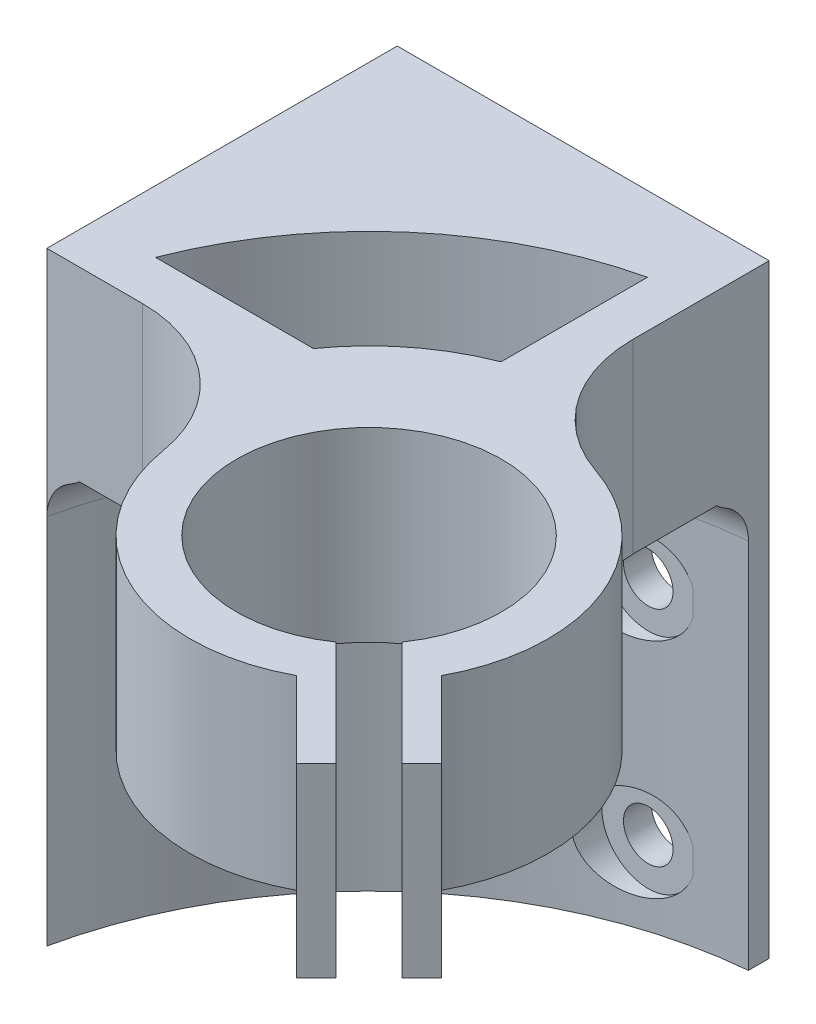
SolidWorks part; units mm, degrees
ref_plane "Front" through (0, 0, 0) normal (0, 0, 1) x (1, 0, 0)
ref_plane "Top" through (0, 0, 0) normal (0, 1, 0) x (1, 0, 0)
ref_plane "Right" through (0, 0, 0) normal (1, 0, 0) x (0, 0, -1)
sketch "Sketch1" plane through (0, 0, 0) normal (0, 1, 0) x (1, 0, 0)
  line L1 (-20, -5) -> (20, -5)
  line L2 (-20, -5) -> (-20, 5)
  line L3 (-20, 5) -> (20, 5)
  line L4 (20, -5) -> (20, 5)
  line L5 (-20, -5) -> (20, 5) construction
  line L6 (-20, 5) -> (20, -5) construction
  point P0 (0, 0)
  dimension "D1" = 40
  dimension "D2" = 10
extrude "Boss-Extrude1" add sketch "Sketch1" along normal blind 65
sketch "Sketch2" plane through (0, 65, 0) normal (0, 1, 0) x (1, 0, 0)
  arc A1 (-20.9979, -42.1234) -> (33.9588, 1.8676) centre (24.0871, -42.1234) ccw construction
sketch "Sketch3" plane through (0, 0, 0) normal (0, -1, 0) x (1, 0, 0)
  line L4 (20, -5) -> (20, 5)
  line L5 (20, 5) -> (-20, 5)
  line L6 (-20, 5) -> (-20, -5)
  line L7 (-20, -5) -> (20, -5)
  line L8 (20, -2.776) -> (20, 5)
  line L9 (20, 5) -> (-1.4963, 5)
  arc A0 (33.9588, -1.8676) -> (-20.9979, 42.1234) centre (24.0871, 42.1234) ccw construction
  arc A2 (-1.4963, 5) -> (20, -2.776) centre (24.0871, 42.1234) ccw
  dimension "D1" = 0
extrude "Cut-Extrude2" cut sketch "Sketch3" against normal up to next
sketch "Sketch4" plane through (0, 0, 0) normal (0, -1, 0) x (-1, 0, 0)
  line L0 (20, -5) -> (20, -32.6903)
  line L1 (20, -5) -> (1.4963, -5)
  arc A0 (20, -32.6903) -> (1.4963, -5) centre (-24.0871, -42.1234) ccw
extrude "Boss-Extrude2" add sketch "Sketch4" against normal up to surface (65 mm away) up to face at (-0.3995, 65, -0.8322)
sketch "Sketch5" plane through (0, 65, 0) normal (0, 1, 0) x (1, 0, 0)
  line L0 (-20, -32.6903) -> (7.3068, -32.6903)
  line L1 (20, 2.776) -> (20, -23.3123)
  line L2 (24.0871, -42.1234) -> (45.3003, -63.3366) construction
  line L3 (24.0871, -42.1234) -> (24.0871, -61.3734) construction
  line L4 (25.8549, -40.3556) -> (47.0681, -61.5688) construction
  line L5 (35.7749, -50.2756) -> (47.0681, -61.5688)
  line L6 (32.2394, -53.8111) -> (43.5326, -65.1044)
  line L7 (41.0206, -51.2787) -> (49.1894, -59.4475)
  line L8 (33.2424, -59.0569) -> (41.4112, -67.2257)
  line L9 (49.1894, -59.4475) -> (47.0681, -61.5688)
  line L10 (43.5326, -65.1044) -> (41.4112, -67.2257)
  line L11 (30.118, -55.9325) -> (41.4112, -67.2257) construction
  line L12 (37.8962, -48.1543) -> (49.1894, -59.4475) construction
  arc A0 (35.7749, -50.2756) -> (32.2394, -53.8111) centre (24.0871, -42.1234) ccw
  arc A1 (7.3068, -32.6903) -> (33.2424, -59.0569) centre (24.0871, -42.1234) ccw
  arc A2 (20, 2.776) -> (-20, -32.6903) centre (24.0871, -42.1234) ccw construction
  arc A3 (20, 2.776) -> (-20, -32.6903) centre (24.0871, -42.1234) ccw
  circle A4 centre (24.0871, -42.1234) radius 19.25 construction
  arc A5 (41.0206, -51.2787) -> (20, -23.3123) centre (24.0871, -42.1234) ccw
  circle A6 centre (24.0871, -42.1234) radius 14.25 construction
  dimension "D1" = 28.5
  dimension "D3" = 45
  dimension "D4" = 30
  dimension "D2" = 5
  dimension "D5" = 3
  dimension "D6" = 2.5
  dimension "D7" = 3
extrude "Boss-Extrude3" add sketch "Sketch5" against normal blind 20
fillet "Fillet1" radius 15 2 edges at (7.3068, 55, 32.6903) (20, 55, 23.3123)
fillet "Fillet2" radius 5 1 edges at (-5.8237, 45, 8.3891)
sketch "Sketch6" plane through (0, 45, 0) normal (0, -1, 0) x (1, 0, 0)
  line L0 (-13.3093, 27.6903) -> (3.6742, 27.6903)
  line L1 (15, 3.082) -> (15, 18.8334)
  line L2 (-14.8721, 32.6903) -> (-9.7074, 32.6903) construction
  line L3 (20, 9.6584) -> (20, 2.2473) construction
  arc A0 (3.6742, 27.6903) -> (15, 18.8334) centre (24.0871, 42.1234) ccw
  arc A1 (-14.8721, 32.6903) -> (20, 2.2473) centre (24.0871, 42.1234) ccw construction
  arc A2 (-13.3093, 27.6903) -> (15, 3.082) centre (24.0871, 42.1234) ccw
  dimension "D1" = 50
  dimension "D2" = 5
  dimension "D3" = 5
extrude "Cut-Extrude3" cut sketch "Sketch6" against normal up to next
fillet "Fillet3" radius 5 4 edges at (15, 45, 10.9577) (8.6867, 45, 22.4301) (-4.8176, 45, 27.6903) (-2.2107, 45, 11.8706)
sketch "Sketch7" plane through (-12.9072, 0, 12.9072) normal (-0.7071, 0, 0.7071) x (0.7071, 0, 0.7071)
  line L0 (71.0417, 45) -> (71.0417, 65) construction
  line L1 (65.2655, 45) -> (76.8179, 45) construction
  line L2 (65.2655, 65) -> (76.8179, 65) construction
  circle A0 centre (71.0417, 50) radius 2.665
  circle A1 centre (71.0417, 60) radius 2.665
  dimension "D1" = 5.33
  dimension "D2" = 5
  dimension "D3" = 5
extrude "Cut-Extrude4" cut sketch "Sketch7" against normal up to surface (11 mm away) up to face at (45.105, 55, 55.3631)
sketch "Sketch8" plane through (0, 0, -5) normal (0, 0, -1) x (-1, 0, 0)
  line L0 (-20, 40) -> (20, 40) construction
  line L1 (-20, 40) -> (20, 40) construction
  line L2 (-10, 40) -> (-10, 32) construction
  line L3 (0, 40) -> (0, 0) construction
  line L4 (-20, 0) -> (20, 0) construction
  line L5 (0, 20) -> (-20, 20) construction
  line L6 (-20, 65) -> (-20, 0) construction
  circle A0 centre (-10, 32) radius 2.665
  circle A1 centre (-10, 8) radius 2.665
  circle A2 centre (10, 8) radius 2.665
  circle A3 centre (10, 32) radius 2.665
  point P19 (0, 0)
  dimension "D2" = 5.33
  dimension "D1" = 8
  dimension "D3" = 10
extrude "Cut-Extrude5" cut sketch "Sketch8" against normal up to next contours A1 | A0 | A3 region at (10, 32, -5) region at (10, 8, -5) region at (-10, 32, -5)
ref_plane "Plane1" through (0, 0, -2) normal (0, 0, -1) x (-1, 0, 0)
sketch "Sketch9" plane through (0, 0, -2) normal (0, 0, -1) x (-1, 0, 0)
  circle A0 centre (-10, 8) radius 5
  circle A1 centre (10, 8) radius 5
  circle A2 centre (10, 32) radius 5
  circle A3 centre (-10, 32) radius 5
  point P12 (0, 0)
  dimension "D1" = 10
extrude "Cut-Extrude6" cut sketch "Sketch9" against normal up to next contours A0 | A3 | A2 region at (10, 8, -2) region at (-10, 32, -2) region at (10, 32, -2)
sketch "Sketch10" plane through (0, 0, 0) normal (0, -1, 0) x (-1, 0, 0)
  line L0 (-20, 2.776) -> (-20, 5) construction
  line L1 (-20, 5) -> (20, 5) construction
  line L2 (20, 5) -> (5.8237, -8.3891) construction
  line L3 (1, 0) -> (14.706, 0) construction
  line L4 (14.706, 0) -> (14.706, -12) construction
  circle A0 centre (1, 0) radius 2.5
  arc A1 (20, -32.6903) -> (-20, 2.776) centre (-24.0871, -42.1234) ccw construction
  circle A2 centre (14.706, 0) radius 2.5
  circle A3 centre (14.706, -12) radius 2.5
  dimension "D1" = 5
  dimension "D2" = 21
  dimension "D3" = 5
  dimension "D4" = 12
extrude "Cut-Extrude7" cut sketch "Sketch10" against normal blind 10
sketch "Sketch12" plane through (-20, 0, 0) normal (-1, 0, 0) x (0, 0, 1)
  line L0 (5, 0) -> (5, 65) construction
  line L1 (-5, 0) -> (32.6903, 0) construction
  line L2 (87.2084, 65) -> (-1.8676, 65) construction
  line L3 (-5, 65) -> (-5, 0) construction
  line L4 (9.5, 0) -> (14.5, 0) construction
  line L5 (-5, 65) -> (32.6903, 65) construction
  circle A0 centre (5, 15) radius 3
  circle A1 centre (5, 50) radius 3
  dimension "D2" = 6
  dimension "D3" = 15
  dimension "D4" = 15
  dimension "D1" = 10
extrude "Cut-Extrude8" cut sketch "Sketch12" against normal blind 10
